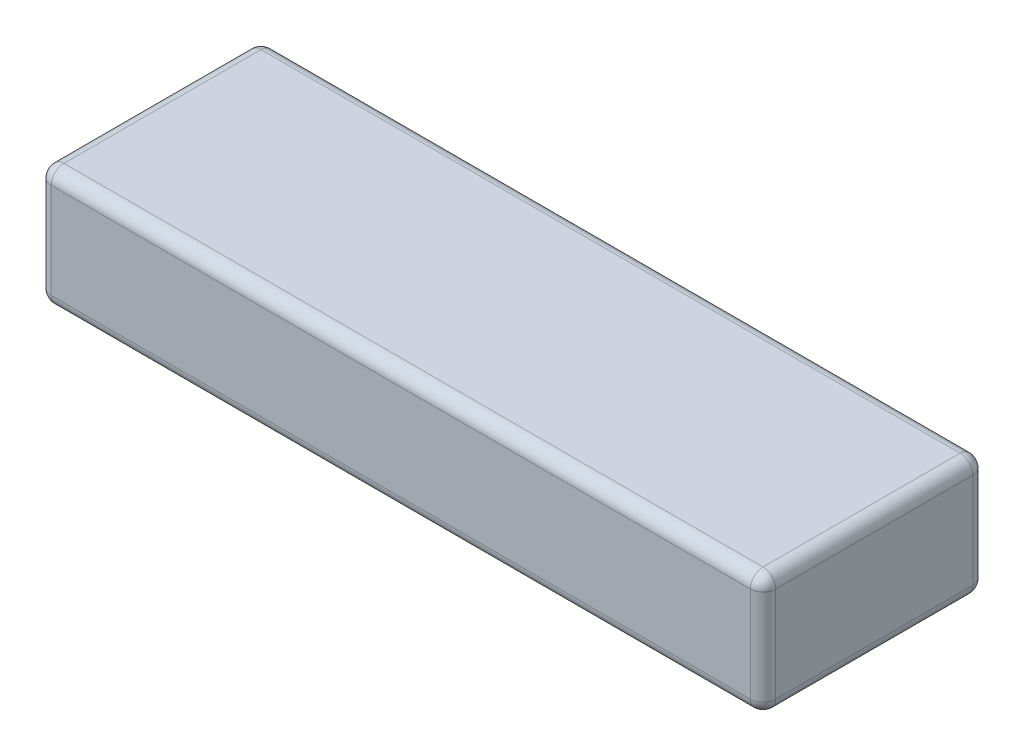
SolidWorks part; units mm, degrees
ref_plane "Plano frontal" through (0, 0, 0) normal (0, 0, 1) x (1, 0, 0)
ref_plane "Plano superior" through (0, 0, 0) normal (0, 1, 0) x (1, 0, 0)
ref_plane "Plano direito" through (0, 0, 0) normal (1, 0, 0) x (0, 0, -1)
sketch "Esboço1" plane through (0, 0, 0) normal (0, 1, 0) x (1, 0, 0)
  line L1 (0, 0) -> (114, 0)
  line L2 (0, 0) -> (0, 35)
  line L3 (0, 35) -> (114, 35)
  line L4 (114, 0) -> (114, 35)
  dimension "D1" = 114
  dimension "D2" = 35
extrude "Ressalto-extrusão1" add sketch "Esboço1" along normal blind 19
fillet "Filete1" radius 2 8 edges at (57, 0, 0) (114, 0, -17.5) (57, 0, -35) (0, 0, -17.5) (57, 19, -35) (114, 19, -17.5) (57, 19, 0) (0, 19, -17.5)
fillet "Filete2" radius 2 12 edges at (0.5858, 18.4142, -0.5858) (0.5858, 0.5858, -0.5858) (0.5858, 18.4142, -34.4142) (0.5858, 0.5858, -34.4142) (113.4142, 18.4142, -34.4142) (113.4142, 0.5858, -34.4142) (113.4142, 18.4142, -0.5858) (113.4142, 0.5858, -0.5858) (0, 9.5, 0) (0, 9.5, -35) (114, 9.5, -35) (114, 9.5, 0)
